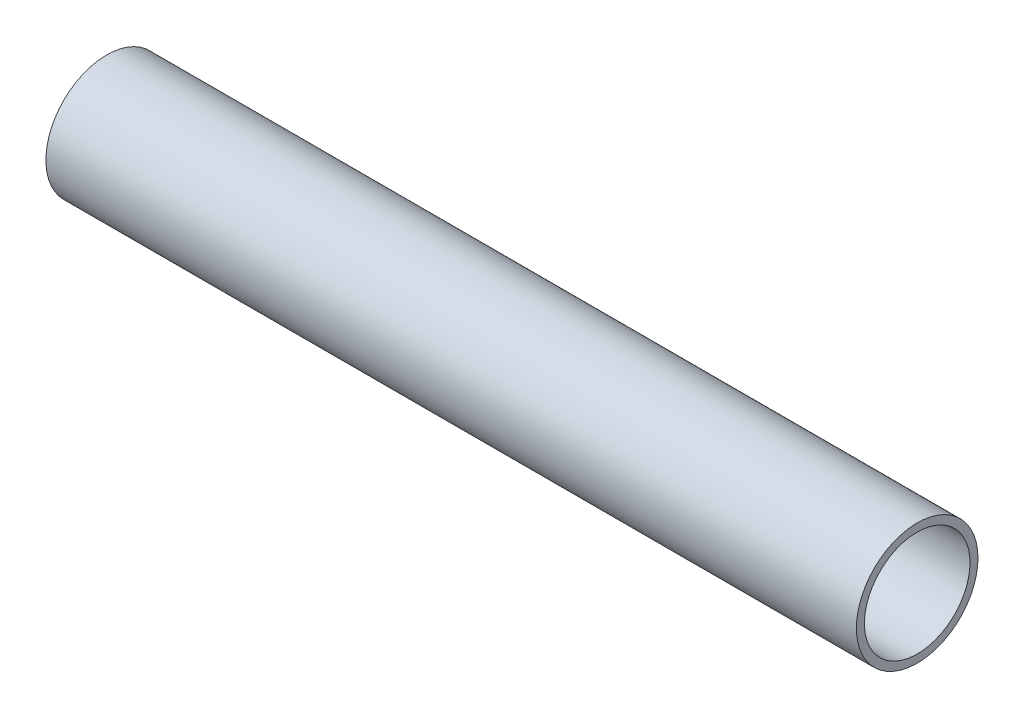
SolidWorks part; units mm, degrees
ref_plane "Front Plane" through (0, 0, 0) normal (1, 0, 0) x (0, 1, 0)
ref_plane "Top Plane" through (0, 0, 0) normal (0, 0, 1) x (0, 1, 0)
ref_plane "Right Plane" through (0, 0, 0) normal (0, 1, 0) x (-1, 0, 0)
sketch "Sketch1" plane through (0, 0, 0) normal (1, 0, 0) x (0, 1, 0)
  circle A0 centre (0, 0) radius 76.2
  circle A1 centre (0, 0) radius 66.2
  dimension "D1" = 152.4
  dimension "D2" = 10
extrude "Boss-Extrude1" add sketch "Sketch1" along normal blind 1016
